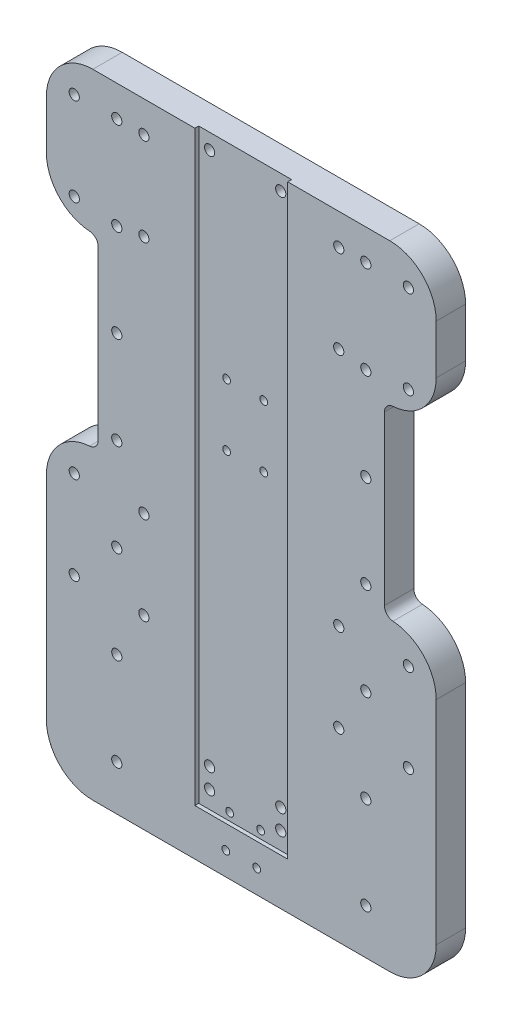
SolidWorks part; units mm, degrees
ref_plane "Piano frontale" through (0, 0, 0) normal (0, 0, 1) x (1, 0, 0)
ref_plane "Piano superiore" through (0, 0, 0) normal (0, 1, 0) x (1, 0, 0)
ref_plane "Piano destro" through (0, 0, 0) normal (1, 0, 0) x (0, 0, -1)
sketch "Schizzo1" plane through (0, 0, 0) normal (0, 0, 1) x (1, 0, 0)
  line L1 (126, -250) -> (-126, -250)
  line L2 (126, -250) -> (126, 250)
  line L3 (126, 250) -> (-126, 250)
  line L4 (-126, -250) -> (-126, 250)
  line L5 (126, -250) -> (-126, 250) construction
  line L6 (126, 250) -> (-126, -250) construction
  point P0 (0, 0)
  dimension "D1" = 252
  dimension "D2" = 500
extrude "Estrusione-Estrusione1" add sketch "Schizzo1" along normal blind 19
sketch "Schizzo2" plane through (0, 0, 19) normal (0, 0, 1) x (1, 0, 0)
  line L0 (1265.2426, 21.4119) -> (-695.7574, 21.4119) construction
  line L1 (1265.2426, 13.5541) -> (-695.7574, 13.5541) construction
  line L2 (1265.2426, 53.5541) -> (-695.7574, 53.5541) construction
  line L3 (1265.2426, 61.4119) -> (-695.7574, 61.4119) construction
  line L4 (-126, 250) -> (-126, -250)
  line L5 (-126, -250) -> (126, -250)
  line L6 (126, -250) -> (126, 250)
  line L7 (126, 250) -> (-126, 250)
  line L8 (-126, 250) -> (-126, -250) construction
  line L9 (-126, -250) -> (126, -250) construction
  line L10 (126, -250) -> (126, 250) construction
  line L11 (126, 250) -> (-126, 250) construction
  line L12 (1265.2426, 21.4119) -> (-695.7574, 21.4119) construction
  line L13 (1265.2426, 13.5541) -> (-695.7574, 13.5541) construction
  line L14 (1265.2426, 53.5541) -> (-695.7574, 53.5541) construction
  line L15 (1265.2426, 61.4119) -> (-695.7574, 61.4119) construction
  line L16 (126, -45.017) -> (-126, -45.017) construction
  line L17 (126, -25.017) -> (-126, -25.017) construction
  line L18 (126, -45.017) -> (-126, -45.017) construction
  line L19 (126, -25.017) -> (-126, -25.017) construction
  line L20 (-126, -45.017) -> (-126, -25.017) construction
  line L21 (126, -35.017) -> (-126, -35.017) construction
  line L22 (-126, -45.017) -> (126, -45.017) construction
  line L23 (-126, -45.017) -> (-126, -25.017) construction
  line L24 (-126, -25.017) -> (126, -25.017) construction
  line L25 (126, -45.017) -> (126, -25.017) construction
  circle A0 centre (110, 17.483) radius 3.9289
  circle A1 centre (110, 57.483) radius 3.9289
  circle A2 centre (-110, 17.483) radius 3.9289
  circle A3 centre (-110, 57.483) radius 3.9289
  circle A4 centre (110, -35.017) radius 3.5
  circle A5 centre (-110, -35.017) radius 3.5
  circle A6 centre (55, -35.017) radius 3.5
  circle A8 centre (-55, -35.017) radius 3.5
  circle A9 centre (20, -35.017) radius 3.5
  circle A10 centre (-20, -35.017) radius 3.5
  circle A11 centre (165, -35.017) radius 3.5 [skipped]
  dimension "D2" = 16
  dimension "D3" = 7.8579
  dimension "D4" = 16
  dimension "D5" = 7.8579
  dimension "D6" = 7
  dimension "D7" = 7
  dimension "D8" = 2
  dimension "D1" = 0
  dimension "D9" = 2
  dimension "D10" = 2
  dimension "D11" = 2
sketch "Schizzo3" plane through (0, 250, 0) normal (0, 1, 0) x (1, 0, 0)
  line L0 (126, -19) -> (-126, -19) construction
  line L1 (30, -16.5) -> (-30, -16.5)
  line L2 (30, -16.5) -> (30, -19)
  line L3 (30, -19) -> (-30, -19)
  line L4 (-30, -16.5) -> (-30, -19)
  line L5 (126, -19) -> (126, 0) construction
  line L6 (-126, -19) -> (-126, 0) construction
  line L7 (126, -19) -> (-126, -19) construction
  dimension "D1" = 2.5
  dimension "D2" = 96
  dimension "D3" = 96
extrude "Taglio-Estrusione1" cut sketch "Schizzo3" against normal through all
sketch "Schizzo4" plane through (0, 0, 16.5) normal (0, 0, 1) x (1, 0, 0)
  line L0 (30, -250) -> (30, 250) construction
  line L2 (30, 250) -> (-30, 250) construction
  line L3 (30, -250) -> (30, 250) construction
  line L6 (-30, 250) -> (-126, 250) construction
  line L7 (-30, -250) -> (-30, 250) construction
  point P11 (23, -118)
  point P14 (-23, -118)
  point P15 (-23, -105)
  point P16 (23, -105)
  point P17 (23, 240)
  point P18 (-23, 240)
  dimension "D1" = 46
  dimension "D2" = 13
  dimension "D3" = 13
  dimension "D4" = 46
  dimension "D5" = 7
  dimension "D6" = 345
  dimension "D7" = 10
  dimension "D8" = 46
  dimension "D9" = 7
  dimension "D10" = 10
  dimension "D11" = 7
  dimension "D12" = 7
sketch "Schizzo5" plane through (0, 0, 19) normal (0, 0, 1) x (1, 0, 0)
  point P4 (80.5006, 170)
  point P7 (80.5006, 110)
  point P16 (80.5006, 50)
  point P17 (80.5006, -10)
  point P18 (80.5006, -70)
  point P19 (80.5006, -130)
  point P20 (80.5006, 230)
hole_wizard "M6 Clearance Hole2" positions "Sketch7" profile "Sketch8" hole size "M6" standard "ISO"
sketch "Sketch7" plane through (0, 0, 19) normal (0, 0, 1) x (1, 0, 0)
  point P0 (80.5006, -130)
  point P3 (80.5006, -70)
  point P7 (80.5006, -10)
  point P10 (80.5006, 50)
  point P13 (80.5006, 110)
  point P16 (80.5006, 170)
  point P19 (80.5006, 230)
sketch "Sketch8" plane through (80.5006, -130, 19) normal (1, 0, 0) x (0, -1, 0)
  line L0 (0, 0) -> (0, 38.5828)
  line L1 (0, 38.5828) -> (3.3, 36.6)
  line L2 (3.3, 36.6) -> (3.3, 0)
  line L5 (3.3, 0) -> (0, 0)
  line L10 (0, 38.5828) -> (-3.3, 36.6) construction
  line L11 (0, -6.35) -> (0, 107.95) construction
  dimension "Hole Dia." = 6.6
  dimension "Hole Depth" = 36.6
  dimension "Drill Angle" = 118
sketch "Schizzo6" plane through (0, 0, 19) normal (0, 0, 1) x (1, 0, 0)
  line L0 (126, -250) -> (126, 250) construction
  line L2 (126, 250) -> (30, 250) construction
  point P23 (108, 172.8083)
  point P26 (63, 172.8083)
  point P27 (63, 229.8083)
  point P28 (108, 229.8083)
  dimension "D1" = 45
  dimension "D2" = 45
  dimension "D3" = 57
  dimension "D4" = 57
  dimension "D5" = 18
  dimension "D6" = 20.1917
  dimension "D7" = 20.1917
  dimension "D8" = 18
hole_wizard "M6 Clearance Hole4" positions "Sketch14" profile "Sketch15" hole size "M6" standard "ISO"
sketch "Sketch14" plane through (0, 0, 19) normal (0, 0, 1) x (1, 0, 0)
  point P0 (108, 172.8083)
  point P3 (108, 229.8083)
  point P6 (63, 229.8083)
  point P9 (63, 172.8083)
  point P12 (63, 17.8083)
  point P14 (63, -39.1917)
  point P16 (108, -39.1917)
  point P18 (108, 17.8083)
sketch "Sketch15" plane through (108, 172.8083, 19) normal (1, 0, 0) x (0, -1, 0)
  line L0 (0, 0) -> (0, 38.5828)
  line L1 (0, 38.5828) -> (3.3, 36.6)
  line L2 (3.3, 36.6) -> (3.3, 0)
  line L5 (3.3, 0) -> (0, 0)
  line L10 (0, 38.5828) -> (-3.3, 36.6) construction
  line L11 (0, -6.35) -> (0, 107.95) construction
  dimension "Hole Dia." = 6.6
  dimension "Hole Depth" = 36.6
  dimension "Drill Angle" = 118
hole_wizard "M6 Clearance Hole3" positions "Sketch9" profile "Sketch10" hole size "M6" standard "ISO"
sketch "Sketch9" plane through (0, 0, 16.5) normal (0, 0, 1) x (1, 0, 0)
  point P0 (23, -118)
  point P3 (23, -105)
  point P6 (-23, -118)
  point P9 (-23, -105)
  point P12 (23, 240)
  point P15 (-23, 240)
sketch "Sketch10" plane through (23, -118, 16.5) normal (1, 0, 0) x (0, -1, 0)
  line L0 (0, 0) -> (0, 38.5828)
  line L1 (0, 38.5828) -> (3.3, 36.6)
  line L2 (3.3, 36.6) -> (3.3, 0)
  line L5 (3.3, 0) -> (0, 0)
  line L10 (0, 38.5828) -> (-3.3, 36.6) construction
  line L11 (0, -6.35) -> (0, 107.95) construction
  dimension "Hole Dia." = 6.6
  dimension "Hole Depth" = 36.6
  dimension "Drill Angle" = 118
sketch "Sketch11" plane through (0, 0, 16.5) normal (0, 0, 1) x (1, 0, 0)
  line L0 (0, -250) -> (0, 250) construction
  line L1 (30, -250) -> (-30, -250) construction
  line L2 (30, 250) -> (-30, 250) construction
ref_plane "Plane1" through (0, 0, 0) normal (-1, 0, 0) x (0, 0, 1)
mirror "Mirror1" about plane through (0, 0, 0) normal (-1, 0, 0) of "M6 Clearance Hole2"
mirror "Mirror2" about plane through (0, 0, 0) normal (-1, 0, 0) of "M6 Clearance Hole4"
sketch "Sketch16" plane through (0, 0, 0) normal (0, 0, -1) x (-1, 0, 0)
  line L0 (126, 250) -> (126, -250) construction
  line L1 (126, -317.9299) -> (-126, -317.9299)
  line L2 (126, -317.9299) -> (126, -159.25)
  line L3 (126, -159.25) -> (-126, -159.25)
  line L4 (-126, -317.9299) -> (-126, -159.25)
  line L5 (-126, -250) -> (-126, 250) construction
  line L9 (-12.9, -159.25) -> (25.2, -159.25) construction
extrude "Cut-Extrude1" cut sketch "Sketch16" against normal blind 28
sketch "Sketch26" plane through (0, 0, 16.5) normal (0, 0, 1) x (1, 0, 0)
  line L0 (30, -159.25) -> (30, 250) construction
  line L1 (-30, -159.25) -> (30, -159.25)
  line L2 (-30, -159.25) -> (-30, -129.25)
  line L3 (-30, -129.25) -> (30, -129.25)
  line L4 (30, -159.25) -> (30, -129.25)
  dimension "D1" = 30
extrude "Boss-Extrude1" add sketch "Sketch26" along normal up to surface (2.5 mm away) up to face at (-78, 45.375, 19)
hole_wizard "Tap Drill for M6 Tap1" positions "Sketch17" profile "Sketch18" hole size "M6" standard "ISO" end condition through all
sketch "Sketch17" plane through (0, 0, 16.5) normal (0, 0, 1) x (1, 0, 0)
  line L0 (12, 77.3083) -> (-12, 117.3083) construction
  line L1 (-12, 117.3083) -> (-12, 77.3083) construction
  line L2 (-12, 77.3083) -> (12, 117.3083) construction
  line L3 (12, 117.3083) -> (12, 77.3083) construction
  line L4 (12, 77.3083) -> (-12, 77.3083) construction
  line L7 (-12, 117.3083) -> (12, 117.3083) construction
  point P0 (-12, 77.3083)
  point P2 (12, 77.3083)
  point P4 (12, 117.3083)
  point P6 (-12, 117.3083)
  dimension "D1" = 40
  dimension "D2" = 24
sketch "Sketch18" plane through (-12, 77.3083, 16.5) normal (1, 0, 0) x (0, -1, 0)
  line L0 (0, 0) -> (0, 16.5)
  line L1 (0, 16.5) -> (2.5, 16.5)
  line L2 (2.5, 16.5) -> (2.5, 0)
  line L5 (2.5, 0) -> (0, 0)
  line L11 (0, -6.35) -> (0, 107.95) construction
  dimension "Thru Hole Dia." = 5
  dimension "Thru Hole Depth" = 16.5
sketch "Sketch19" plane through (0, -195.45, 0) normal (0, -1, 0) x (-1, 0, 0)
  line L0 (0, -70.7) -> (0, 68.239) construction
  line L1 (126, -9.5) -> (-126, -9.5) construction
  line L2 (126, -19) -> (126, 0) construction
  line L3 (-126, -19) -> (-126, 0) construction
  line L5 (28.2, 0) -> (-28.2, 0) construction
  point P8 (20, -9.5)
  point P9 (-20, -9.5)
  point P12 (-20, 9.5)
  point P13 (20, 9.5)
  dimension "D1" = 20
hole_wizard "Tap Drill for M6 Tap2" positions "Sketch22" profile "Sketch23" hole size "M6" standard "ISO"
sketch "Sketch22" plane through (0, -159.25, 0) normal (0, -1, 0) x (-1, 0, 0)
  point P0 (20, -9.125)
  point P2 (-20, -9.125)
sketch "Sketch23" plane through (-20, -159.25, 9.125) normal (1, 0, 0) x (0, 0, -1)
  line L0 (0, 0) -> (0, 31.5022)
  line L1 (0, 31.5022) -> (2.5, 30)
  line L2 (2.5, 30) -> (2.5, 0)
  line L5 (2.5, 0) -> (0, 0)
  line L10 (0, 31.5022) -> (-2.5, 30) construction
  line L11 (0, -6.35) -> (0, 107.95) construction
  dimension "Hole Dia." = 5
  dimension "Hole Depth" = 30
  dimension "Drill Angle" = 118
hole_wizard "Tap Drill for M6 Tap3" positions "Sketch24" profile "Sketch25" hole size "M6" standard "ISO" end condition through all
sketch "Sketch24" plane through (0, 0, 0) normal (0, 0, -1) x (-1, 0, 0)
  point P0 (-10, -144.25)
  point P2 (-10, -124.25)
  point P4 (10, -124.25)
  point P6 (10, -144.25)
sketch "Sketch25" plane through (10, -144.25, 0) normal (1, 0, 0) x (0, 1, 0)
  line L0 (0, 0) -> (0, 19)
  line L1 (0, 19) -> (2.5, 19)
  line L2 (2.5, 19) -> (2.5, 0)
  line L5 (2.5, 0) -> (0, 0)
  line L11 (0, -6.35) -> (0, 107.95) construction
  dimension "Thru Hole Dia." = 5
  dimension "Thru Hole Depth" = 19
sketch "Sketch27" plane through (0, 0, 19) normal (0, 0, 1) x (1, 0, 0)
  line L2 (-126, 38.082) -> (-126, 158.222)
  line L4 (-92.5, 38.082) -> (-92.5, 158.222)
  line L5 (-126, 38.082) -> (-92.5, 38.082)
  line L7 (-126, 158.222) -> (-92.5, 158.222)
  line L9 (-92.5, 40.082) -> (-92.5, 156.222) construction
  line L10 (-126, 40.082) -> (-126, 156.222) construction
  line L11 (-128, 158.222) -> (-90.5, 158.222) construction
  line L12 (-128, 38.082) -> (-128, 158.222) construction
  line L13 (-128, 38.082) -> (-90.5, 38.082) construction
  line L14 (-126, 40.082) -> (-92.5, 40.082) construction
  line L15 (-90.5, 38.082) -> (-90.5, 158.222) construction
  line L16 (-126, 156.222) -> (-92.5, 156.222) construction
  line L17 (-126, 98.152) -> (126, 98.152) construction
  line L18 (126, -159.25) -> (126, 250) construction
  line L19 (126, 98.152) -> (0, 98.152) construction
  line L20 (0, 98.152) -> (0, 87.9155) construction
  line L21 (-126, 38.082) -> (-92.5, 38.082)
  line L22 (-126, 158.222) -> (-92.5, 158.222)
  line L23 (126, 158.222) -> (92.5, 158.222)
  line L24 (126, 38.082) -> (92.5, 38.082)
  line L25 (126, 158.222) -> (92.5, 158.222)
  line L26 (126, 38.082) -> (92.5, 38.082)
  line L27 (92.5, 38.082) -> (92.5, 158.222)
  line L28 (126, 38.082) -> (126, 158.222)
  line M11 (-126, 250) -> (-126, -159.25)
  line M13 (126, -159.25) -> (126, 250)
  dimension "D1" = 2
extrude "Cut-Extrude2" cut sketch "Sketch27" against normal blind 76.9911 contours L27 L24 L23 M13 | L7 L5 L4 M11 region at (-109.25, 98.152, 19) region at (109.25, 98.152, 19)
fillet "Fillet1" radius 30 4 edges at (126, 158.222, 9.5) (126, 38.082, 9.5) (-126, 158.222, 9.5) (-126, 38.082, 9.5)
fillet "Fillet2" radius 30 4 edges at (126, 250, 9.5) (-126, 250, 9.5) (-126, -159.25, 9.5) (126, -159.25, 9.5)
fillet "Fillet3" radius 6 4 edges at (92.5, 158.222, 9.5) (92.5, 38.082, 9.5) (-92.5, 38.082, 9.5) (-92.5, 158.222, 9.5)
equation "\"D3@Schizzo3\"=\"D2@Schizzo3\""
equation "\"D11@Schizzo4\"=\"D5@Schizzo4\""
